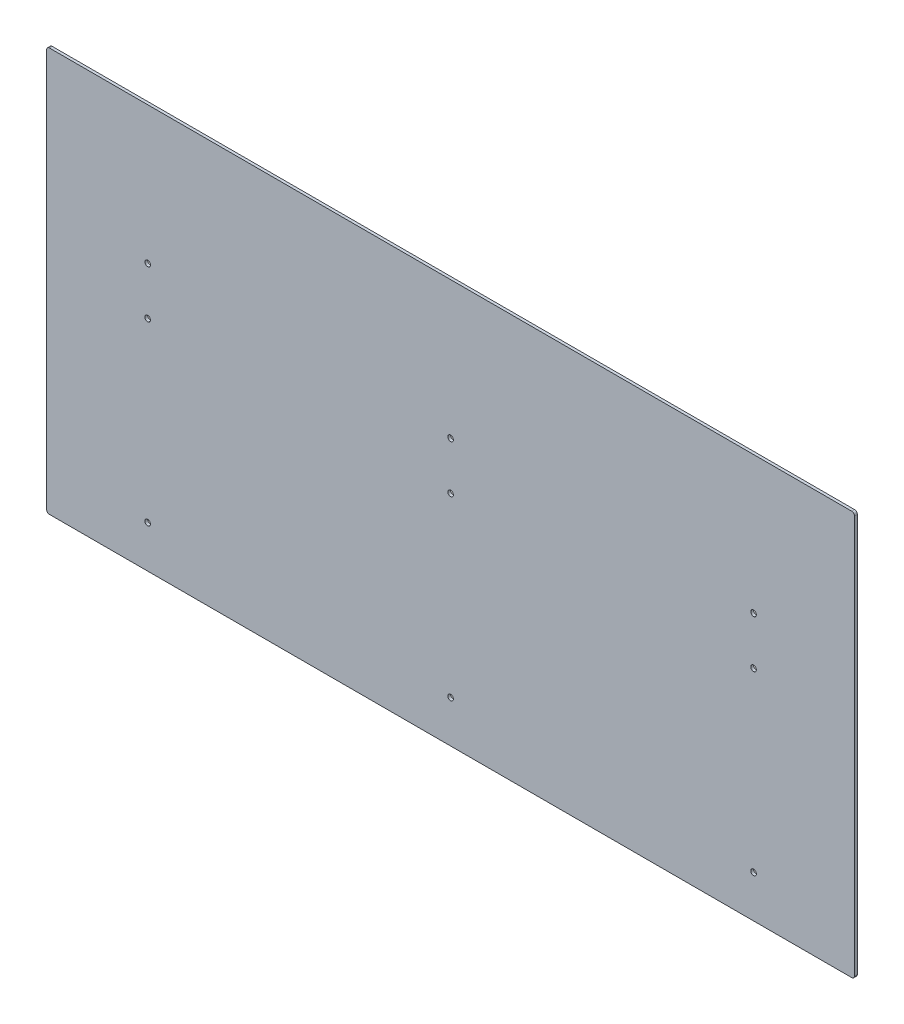
SolidWorks part; units mm, degrees
material "PC High Viscosity"
ref_plane "Front Plane" through (0, 0, 0) normal (0, 0, 1) x (1, 0, 0)
ref_plane "Top Plane" through (0, 0, 0) normal (0, 1, 0) x (1, 0, 0)
ref_plane "Right Plane" through (0, 0, 0) normal (1, 0, 0) x (0, 0, -1)
sketch "Sketch1" plane through (0, 0, 0) normal (0, 0, 1) x (1, 0, 0)
  line L1 (0, 0) -> (914.4, 0)
  line L2 (0, 0) -> (0, 457.2)
  line L3 (0, 457.2) -> (914.4, 457.2)
  line L4 (914.4, 0) -> (914.4, 457.2)
  dimension "D1" = 457.2
  dimension "D2" = 914.4
extrude "Boss-Extrude1" add sketch "Sketch1" along normal blind 3.175
sketch "Sketch2" plane through (0, 0, 3.175) normal (0, 0, 1) x (1, 0, 0)
  line L0 (914.4, 300.0375) -> (0, 300.0375)
  line L1 (539.75, 300.0375) -> (539.75, -4.7625)
  line L2 (914.4, 0) -> (914.4, 457.2) construction
  line L3 (0, 457.2) -> (0, 0) construction
  line L4 (914.4, -4.7625) -> (0, -4.7625)
  line L5 (914.4, 46.0375) -> (0, 46.0375)
  line L6 (914.4, 249.2375) -> (0, 249.2375)
  line L7 (374.65, 300.0375) -> (374.65, -4.7625)
  line L11 (457.2, 300.0375) -> (457.2, 457.2) construction
  line L12 (914.4, 457.2) -> (0, 457.2) construction
  line L13 (0, 147.6375) -> (914.4, 147.6375) construction
  line L14 (0, 0) -> (914.4, 0) construction
  dimension "D1" = 50.8
  dimension "D2" = 50.8
  dimension "D3" = 304.8
  dimension "D4" = 374.65
  dimension "D5" = 374.65
  dimension "D6" = 152.4
  dimension "D7" = 4.7625
hole_wizard "1/4 (0.25) Diameter Hole1" positions "Sketch3" profile "Sketch4" hole size "1/4" standard "ANSI Inch" end condition through all
sketch "Sketch3" plane through (0, 0, 3.175) normal (0, 0, 1) x (1, 0, 0)
  line L0 (0, 300.0375) -> (0, 249.2375) construction
  line L1 (0, 457.2) -> (0, 0) construction
  line L3 (914.4, 249.2375) -> (0, 249.2375) construction
  line L4 (0, 274.6375) -> (914.4, 274.6375) construction
  line L6 (914.4, 0) -> (914.4, 457.2) construction
  line L7 (914.4, 249.2375) -> (914.4, 46.0375) construction
  line L8 (914.4, 46.0375) -> (0, 46.0375) construction
  line L9 (914.4, 147.6375) -> (0, 147.6375) construction
  line L10 (457.2, 300.0375) -> (457.2, 457.2) construction
  line L12 (457.2, 457.2) -> (457.2, 0) construction
  line L13 (914.4, 457.2) -> (0, 457.2) construction
  line L14 (0, 0) -> (914.4, 0) construction
  point P0 (114.3, 247.65)
  point P2 (114.3, 301.625)
  point P36 (457.2, 301.625)
  point P38 (457.2, 247.65)
  point P58 (800.1, 247.65)
  point P59 (800.1, 301.625)
  point P61 (114.3, 47.625)
  point P64 (457.2, 47.625)
  point P65 (800.1, 47.625)
  dimension "D1" = 53.975
  dimension "D2" = 114.3
sketch "Sketch4" plane through (114.3, 247.65, 3.175) normal (1, 0, 0) x (0, -1, 0)
  line L0 (0, 0) -> (0, 3.175)
  line L1 (0, 3.175) -> (3.175, 3.175)
  line L2 (3.175, 3.175) -> (3.175, 0)
  line L5 (3.175, 0) -> (0, 0)
  line L11 (0, -6.35) -> (0, 107.95) construction
  dimension "Thru Hole Dia." = 6.35
  dimension "Thru Hole Depth" = 3.175
ref_plane "Plane1" through (0, 147.6375, 0) normal (0, 1, 0) x (1, 0, 0)
fillet "Fillet1" radius 3.175 4 edges at (914.4, 457.2, 1.5875) (914.4, 0, 1.5875) (0, 0, 1.5875) (0, 457.2, 1.5875)
